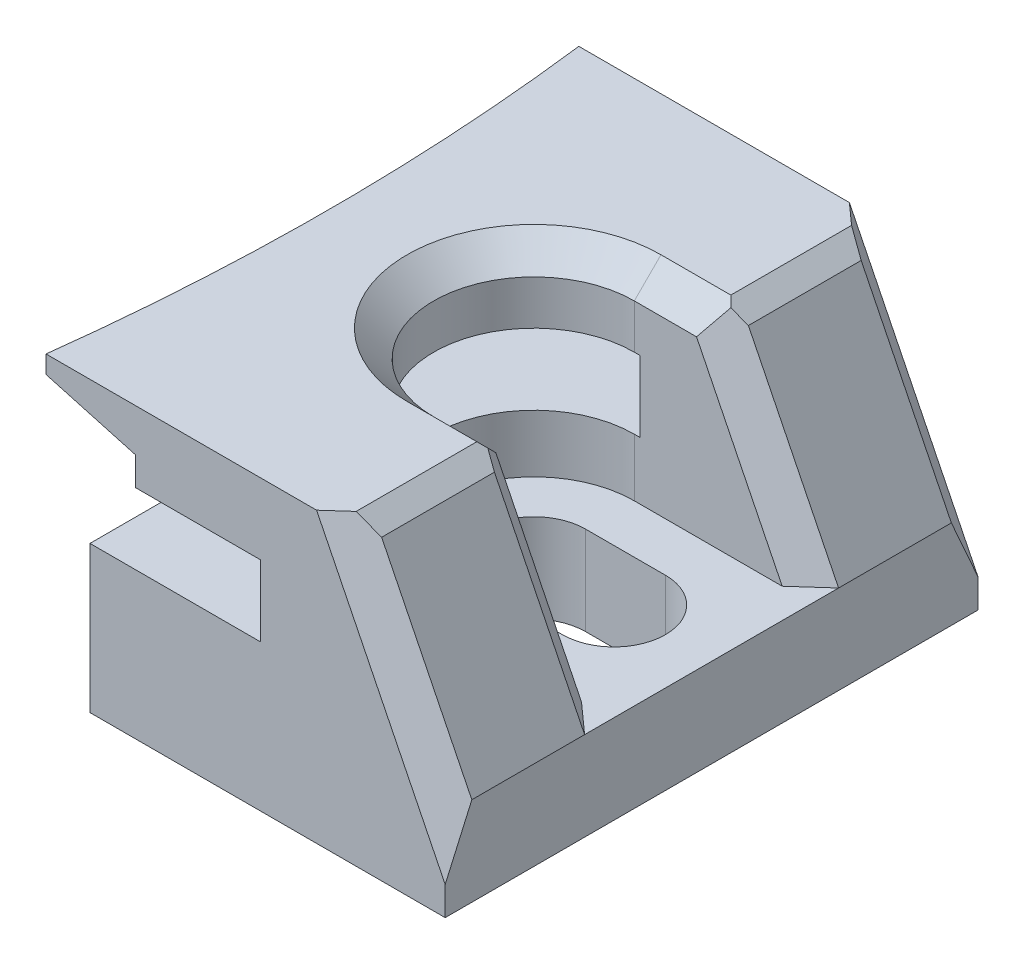
SolidWorks part; units mm, degrees
ref_plane "Front Plane" through (0, 0, 0) normal (0, 0, 1) x (1, 0, 0)
ref_plane "Top Plane" through (0, 0, 0) normal (0, 1, 0) x (1, 0, 0)
ref_plane "Right Plane" through (0, 0, 0) normal (1, 0, 0) x (0, 0, -1)
sketch "Sketch1" plane through (0, 0, 0) normal (0, 0, 1) x (1, 0, 0)
  line L0 (20, 0) -> (0, 0)
  line L1 (0, 0) -> (0, 12.25)
  line L2 (0, 12.25) -> (-5.155, 12.25)
  line L3 (14.4328, 16.25) -> (-5.155, 16.25)
  line L4 (-5.155, 16.25) -> (-5.155, 12.25)
  line L6 (14.4328, 16.25) -> (20, 5)
  line L7 (20, 5) -> (20, 0)
  line L8 (0, 0) -> (-123.55, 0)
  dimension "D1" = 20
  dimension "D2" = 12.25
  dimension "D3" = 143.55
  dimension "D4" = 5
  dimension "D5" = 4
extrude "Boss-Extrude1" add sketch "Sketch1" along normal blind 15 and the other way blind 15 contours L7 L6 L3 L4 L2 L1 L0 region at (8.3634, 8.0909, 0)
sketch "Sketch2" plane through (0, 0, 0) normal (0, 0, 1) x (1, 0, 0)
  line L0 (-5.155, 16.25) -> (-1.55, 16.25)
  line L1 (0, 12.25) -> (10.45, 12.25)
  line L2 (0, 12.25) -> (0, 8.25)
  line L3 (0, 8.25) -> (10.45, 8.25)
  line L4 (10.45, 12.25) -> (10.45, 8.25)
  line L5 (0, 12.25) -> (-5.155, 12.25) construction
  line L6 (-5.155, 16.25) -> (-5.155, 12.25) construction
  line L7 (14.4328, 16.25) -> (-5.155, 16.25) construction
  line L8 (-5.155, 16.25) -> (-5.155, 12.25)
  line L9 (-5.155, 12.25) -> (3.45, 12.25)
  line L10 (-123.55, 0) -> (-123.55, 17.4525)
  line L12 (-1.55, 16.25) -> (-1.55, 15.25)
  line L13 (-1.55, 15.25) -> (3.45, 13.85)
  line L14 (3.45, 13.85) -> (3.45, 12.25)
  line L15 (0, 12.25) -> (-5.155, 12.25) construction
  dimension "D1" = 134
  dimension "D2" = 4
  dimension "D3" = 5
  dimension "D4" = 127
  dimension "D5" = 3
  dimension "D6" = 1.6
revolve "Cut-Revolve2" cut sketch "Sketch2" angle 360 about L10 region at (-1.5561, 13.8886, 0) region at (5.225, 10.25, 0)
ref_plane "Plane1" through (0, 5, 0) normal (0, -1, 0) x (-1, 0, 0)
sketch "Sketch5" plane through (0, 5, 0) normal (0, -1, 0) x (-1, 0, 0)
  line L0 (-10, 0) -> (-10, -15) construction
  line L1 (-10, 0) -> (-20, 0) construction
  line L2 (-10, -5.65) -> (-20, -5.65)
  line L3 (-20, -5.65) -> (-20, 5.65)
  line L4 (-20, 15) -> (-20, -15)
  line L5 (-20, -15) -> (0, -15)
  line L6 (0, -15) -> (0, 15)
  line L7 (0, 15) -> (-20, 15)
  line L8 (-20, 15) -> (-20, -15)
  line L9 (-20, -15) -> (0, -15)
  line L10 (0, -15) -> (0, 15)
  line L11 (0, 15) -> (-20, 15)
  line L12 (-20, 5.65) -> (-10, 5.65)
  arc A0 (-10, -5.65) -> (-10, 5.65) centre (-10, 0) ccw
  dimension "D2" = 11.3
  dimension "D1" = 0
extrude "Cut-Extrude3" cut sketch "Sketch5" against normal through all contours A0 region at (12.7262, 5, 0)
sketch "Sketch6" plane through (0, 5, 0) normal (0, 1, 0) x (1, 0, 0)
  line L0 (10, 0) -> (14.5, 0) construction
  line L1 (10, 2.9) -> (14.5, 2.9)
  line L2 (10, -2.9) -> (14.5, -2.9)
  arc A0 (10, 2.9) -> (10, -2.9) centre (10, 0) ccw
  arc A1 (10, 5.65) -> (10, -5.65) centre (10, 0) ccw construction
  arc A3 (14.5, -2.9) -> (14.5, 2.9) centre (14.5, 0) ccw
  point P0 (12.25, 0)
  dimension "D2" = 2.9
  dimension "D3" = 4.5
extrude "Cut-Extrude7" cut sketch "Sketch6" against normal up to surface (5 mm away) up to face at (10, 0, 0)
chamfer "Chamfer1" distance 1.5 angle 45 7 edges at (12.2164, 16.25, 5.65) (12.2164, 16.25, -5.65) (4.35, 16.25, 0) (17.2164, 10.625, -5.65) (17.2164, 10.625, 5.65) (17.2164, 10.625, -15) (17.2164, 10.625, 15)
chamfer "Chamfer2" distance 0.5 angle 45 2 edges at (14.4328, 16.25, 10.325) (14.4328, 16.25, -10.325) first distance on face at (9.2074, 16.25, 0)
